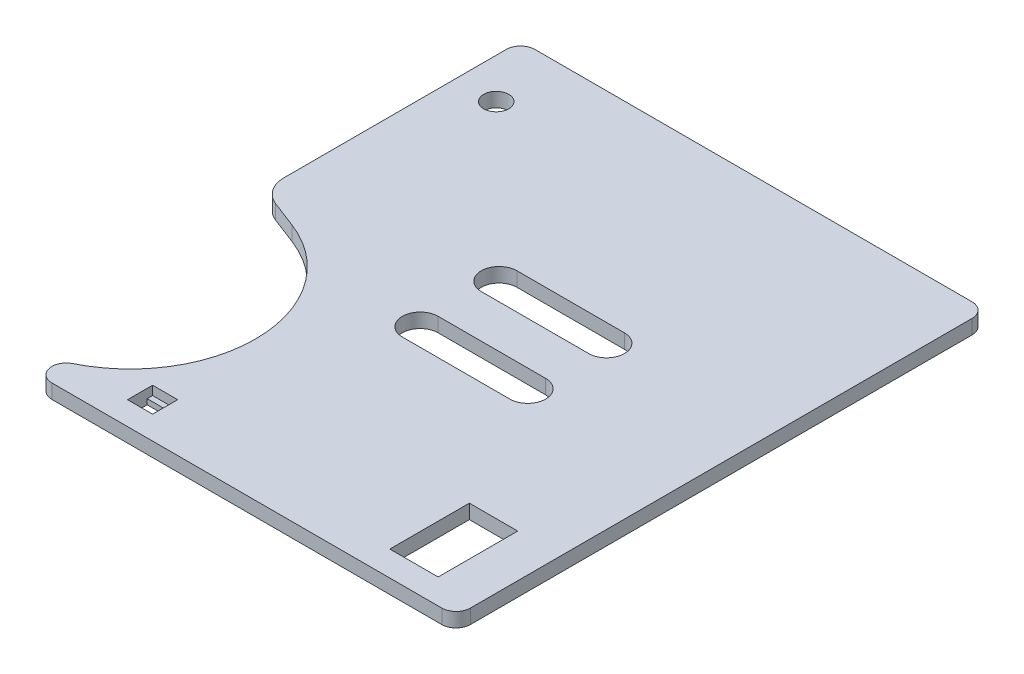
SolidWorks part; units mm, degrees
ref_plane "Front Plane" through (0, 0, 0) normal (0, 0, 1) x (1, 0, 0)
ref_plane "Top Plane" through (0, 0, 0) normal (0, 1, 0) x (1, 0, 0)
ref_plane "Right Plane" through (0, 0, 0) normal (1, 0, 0) x (0, 0, -1)
sketch "Sketch2" plane through (0, 962.2378, 0) normal (0, 1, 0) x (1, 0, 0)
  line L0 (650.9391, -1355.6049) -> (650.9391, -1351.6049) construction
  line L1 (648.0619, -1359.0697) -> (655.5266, -1361.9468)
  line L4 (772.9391, -1429.6049) -> (772.9391, -1289.6049)
  line L5 (768.9391, -1285.6049) -> (646.9391, -1285.6049)
  line L6 (642.9391, -1289.6049) -> (642.9391, -1351.7914)
  line L7 (642.9391, -1433.6049) -> (768.9391, -1433.6049)
  line L8 (772.9391, -1429.6049) -> (772.9391, -1289.6049)
  line L9 (768.9391, -1285.6049) -> (646.9391, -1285.6049)
  line L10 (642.9391, -1289.6049) -> (642.9391, -1351.7914)
  line L11 (642.9391, -1433.6049) -> (768.9391, -1433.6049)
  arc A0 (642.9391, -1351.6049) -> (648.0619, -1359.0697) centre (650.9391, -1351.6049) ccw
  arc A1 (674.026, -1378.5239) -> (674.026, -1410.686) centre (642.9391, -1394.6049) ccw construction
  circle A2 centre (642.9391, -1394.6049) radius 35
  arc A3 (658.3791, -1426.0152) -> (660.1437, -1433.6049) centre (660.1437, -1429.6049) ccw
  arc A5 (772.9391, -1289.6049) -> (768.9391, -1285.6049) centre (768.9391, -1289.6049) ccw
  arc A6 (646.9391, -1285.6049) -> (642.9391, -1289.6049) centre (646.9391, -1289.6049) ccw
  arc A7 (639.3112, -1355.774) -> (642.9391, -1351.7914) centre (638.9391, -1351.7914) ccw
  arc A8 (639.3112, -1355.774) -> (642.9391, -1433.6049) centre (642.9391, -1394.6049) ccw
  arc A9 (768.9391, -1433.6049) -> (772.9391, -1429.6049) centre (768.9391, -1429.6049) ccw
  arc A10 (772.9391, -1289.6049) -> (768.9391, -1285.6049) centre (768.9391, -1289.6049) ccw
  arc A11 (646.9391, -1285.6049) -> (642.9391, -1289.6049) centre (646.9391, -1289.6049) ccw
  arc A12 (639.3112, -1355.774) -> (642.9391, -1351.7914) centre (638.9391, -1351.7914) ccw
  arc A13 (639.3112, -1355.774) -> (642.9391, -1433.6049) centre (642.9391, -1394.6049) ccw
  arc A14 (768.9391, -1433.6049) -> (772.9391, -1429.6049) centre (768.9391, -1429.6049) ccw
  point P28 (0, 0)
  dimension "D1" = 0
extrude "Boss-Extrude1" add sketch "Sketch2" along normal blind 4
sketch "Sketch3" plane through (0, 962.2378, 0) normal (0, -1, 0) x (1, 0, 0)
  line L0 (764.9391, 1289.6049) -> (650.9391, 1289.6049) construction
  line L1 (686.7391, 1429.4049) -> (742.9391, 1429.4049)
  line L2 (686.7391, 1429.4049) -> (686.7391, 1424.4049)
  line L3 (686.7391, 1424.4049) -> (742.9391, 1424.4049)
  line L4 (742.9391, 1429.4049) -> (742.9391, 1424.4049)
  line L5 (686.7391, 1429.6049) -> (686.7391, 1433.6049) construction
  line L6 (742.9391, 1429.6049) -> (742.9391, 1433.6049) construction
  line L7 (742.9391, 1429.6049) -> (686.7391, 1429.6049) construction
  line L8 (707.9391, 1294.8049) -> (707.9391, 1289.8049) construction
  line L9 (682.9391, 1289.8049) -> (732.9391, 1289.8049)
  line L10 (682.9391, 1289.8049) -> (682.9391, 1294.8049)
  line L11 (682.9391, 1294.8049) -> (732.9391, 1294.8049)
  line L12 (732.9391, 1289.8049) -> (732.9391, 1294.8049)
  line L13 (646.9391, 1293.6049) -> (646.9391, 1351.6049) construction
  line L14 (768.9391, 1351.6049) -> (768.9391, 1293.6049) construction
  line L15 (768.9391, 1425.6049) -> (768.9391, 1363.6049) construction
  line L16 (768.7391, 1407.1049) -> (763.7391, 1407.1049)
  line L17 (768.7391, 1407.1049) -> (768.7391, 1382.1049)
  line L18 (768.7391, 1382.1049) -> (763.7391, 1382.1049)
  line L19 (763.7391, 1407.1049) -> (763.7391, 1382.1049)
  line L20 (763.7391, 1394.6049) -> (768.7391, 1394.6049) construction
  line L21 (660.1437, 1429.6049) -> (764.9391, 1429.6049) construction
  line L22 (764.9391, 1359.6049) -> (660.1437, 1359.6049) construction
  line L23 (652.1391, 1322.6049) -> (647.1391, 1322.6049) construction
  line L24 (647.1391, 1335.1049) -> (652.1391, 1335.1049)
  line L25 (647.1391, 1335.1049) -> (647.1391, 1310.1049)
  line L26 (647.1391, 1310.1049) -> (652.1391, 1310.1049)
  line L27 (652.1391, 1335.1049) -> (652.1391, 1310.1049)
  line L28 (764.9391, 1355.6049) -> (650.9391, 1355.6049) construction
  dimension "D1" = 5
  dimension "D2" = 0.2
  dimension "D3" = 0.2
  dimension "D4" = 5
  dimension "D5" = 50
  dimension "D6" = 0.2
  dimension "D7" = 25
  dimension "D8" = 5
  dimension "D9" = 0.2
  dimension "D10" = 5
  dimension "D11" = 25
extrude "Boss-Extrude2" add sketch "Sketch3" along normal blind 4
fillet "Fillet1" radius 3.5 4 edges at (647.1391, 958.2378, 1322.6049) (707.9391, 958.2378, 1289.8049) (768.7391, 958.2378, 1394.6049) (714.8391, 958.2378, 1429.4049)
fillet "Fillet2" radius 2 12 edges at (766.2391, 962.2378, 1382.1049) (766.2391, 962.2378, 1407.1049) (763.7391, 962.2378, 1394.6049) (686.7391, 962.2378, 1426.9049) (714.8391, 962.2378, 1424.4049) (742.9391, 962.2378, 1426.9049) (732.9391, 962.2378, 1292.3049) (682.9391, 962.2378, 1292.3049) (707.9391, 962.2378, 1294.8049) (649.6391, 962.2378, 1335.1049) (649.6391, 962.2378, 1310.1049) (652.1391, 962.2378, 1322.6049)
sketch "Sketch4" plane through (0, 962.2378, 0) normal (0, -1, 0) x (1, 0, 0)
  line L0 (654.1391, 1337.1049) -> (654.1391, 1308.1049) construction
  line L1 (654.1391, 1308.1049) -> (647.1391, 1308.1049) construction
  line L3 (697.9391, 1346.6049) -> (727.9391, 1346.6049) construction
  line L4 (697.9391, 1351.6049) -> (727.9391, 1351.6049)
  line L5 (697.9391, 1341.6049) -> (727.9391, 1341.6049)
  line L6 (697.9391, 1368.6049) -> (727.9391, 1368.6049) construction
  line L7 (697.9391, 1373.6049) -> (727.9391, 1373.6049)
  line L8 (697.9391, 1363.6049) -> (727.9391, 1363.6049)
  line L9 (772.9391, 1429.6049) -> (772.9391, 1289.6049) construction
  line L10 (772.9391, 1429.6049) -> (772.9391, 1289.6049) construction
  line L11 (764.9391, 1355.6049) -> (650.9391, 1355.6049) construction
  line L12 (764.9391, 1359.6049) -> (660.1437, 1359.6049) construction
  line L13 (660.1437, 1429.6049) -> (764.9391, 1429.6049) construction
  line L14 (747.4391, 1426.6049) -> (760.9391, 1426.6049)
  line L15 (747.4391, 1426.6049) -> (747.4391, 1404.4049)
  line L16 (747.4391, 1404.4049) -> (760.9391, 1404.4049)
  line L17 (760.9391, 1426.6049) -> (760.9391, 1404.4049)
  line L18 (768.9391, 1425.6049) -> (768.9391, 1363.6049) construction
  circle A0 centre (654.1391, 1303.6049) radius 3.5
  arc A2 (697.9391, 1351.6049) -> (697.9391, 1341.6049) centre (697.9391, 1346.6049) ccw
  arc A3 (727.9391, 1341.6049) -> (727.9391, 1351.6049) centre (727.9391, 1346.6049) ccw
  arc A4 (697.9391, 1373.6049) -> (697.9391, 1363.6049) centre (697.9391, 1368.6049) ccw
  arc A5 (727.9391, 1363.6049) -> (727.9391, 1373.6049) centre (727.9391, 1368.6049) ccw
  point P4 (712.9391, 1346.6049)
  point P17 (712.9391, 1368.6049)
  dimension "D1" = 7
  dimension "D2" = 13.5
  dimension "D9" = 5
  dimension "D10" = 5
  dimension "D3" = 4.5
  dimension "D4" = 22.2
  dimension "D5" = 30
  dimension "D6" = 30
  dimension "D7" = 60
  dimension "D8" = 60
  dimension "D11" = 4
  dimension "D12" = 4
  dimension "D13" = 3
  dimension "D14" = 8
extrude "Cut-Extrude1" cut sketch "Sketch4" against normal up to next
sketch "Sketch5" plane through (0, 966.2378, 0) normal (0, 1, 0) x (1, 0, 0)
  line L0 (660.1437, -1429.6049) -> (764.9391, -1429.6049) construction
  line L1 (674.7391, -1420.1049) -> (681.7391, -1420.1049)
  line L2 (674.7391, -1420.1049) -> (674.7391, -1427.1049)
  line L3 (674.7391, -1427.1049) -> (681.7391, -1427.1049)
  line L4 (681.7391, -1420.1049) -> (681.7391, -1427.1049)
  line L5 (684.7391, -1422.4049) -> (684.7391, -1429.4049) construction
  dimension "D1" = 7
  dimension "D2" = 7
  dimension "D3" = 2.5
  dimension "D4" = 3
extrude "Cut-Extrude2" cut sketch "Sketch5" against normal blind 2.5
sketch "Sketch6" plane through (0, 963.7378, 0) normal (0, 1, 0) x (1, 0, 0)
  line L0 (674.7391, -1420.1049) -> (674.7391, -1427.1049) construction
  line L1 (674.7391, -1421.6049) -> (681.7391, -1421.6049)
  line L2 (674.7391, -1421.6049) -> (674.7391, -1425.6049)
  line L3 (674.7391, -1425.6049) -> (681.7391, -1425.6049)
  line L4 (681.7391, -1421.6049) -> (681.7391, -1425.6049)
  line L5 (681.7391, -1427.1049) -> (681.7391, -1420.1049) construction
  line L6 (681.7391, -1420.1049) -> (674.7391, -1420.1049) construction
  line L7 (674.7391, -1427.1049) -> (681.7391, -1427.1049) construction
  dimension "D1" = 1.5
  dimension "D2" = 1.5
extrude "Cut-Extrude3" cut sketch "Sketch6" against normal up to next
